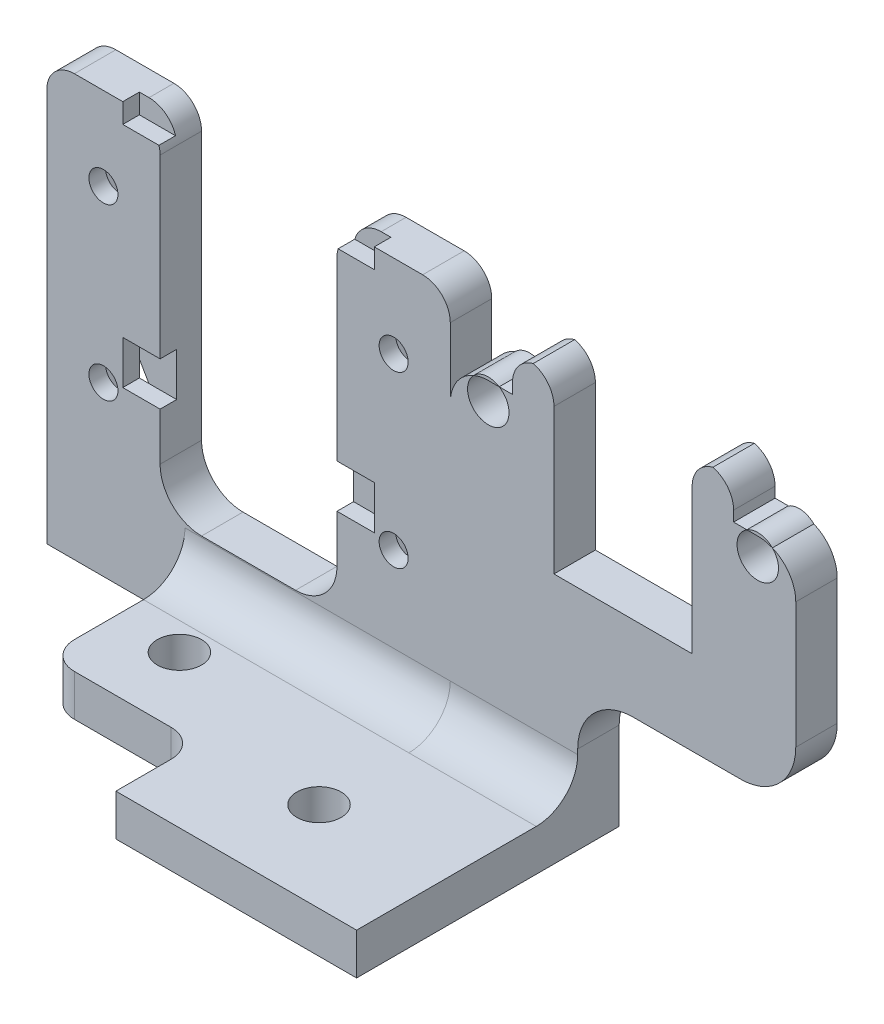
SolidWorks part; units mm, degrees
ref_plane "Plano frontal" through (0, 0, 0) normal (0, 0, 1) x (1, 0, 0)
ref_plane "Plano superior" through (0, 0, 0) normal (0, 1, 0) x (1, 0, 0)
ref_plane "Plano direito" through (0, 0, 0) normal (1, 0, 0) x (0, 0, -1)
sketch "Esboço2" plane through (0, 0, -1) normal (0, 0, -1) x (-1, 0, 0)
  line L1 (14.6, 8.1) -> (6.4, 8.1)
  line L2 (14.6, 8.1) -> (14.6, -22.3604)
  line L3 (14.6, -22.3604) -> (6.4, -22.3604)
  line L4 (6.4, 8.1) -> (6.4, -22.3604)
  line L5 (6.4, 8.1) -> (-21.6025, 8.1) construction
  line L6 (-12.6, -12) -> (-12.6, 12) construction
  line L7 (-14.6, 8.1) -> (-6.4, 8.1)
  line L8 (-14.6, 8.1) -> (-14.6, -22.3604)
  line L9 (-14.6, -22.3604) -> (-6.4, -22.3604)
  line L10 (-6.4, 8.1) -> (-6.4, -22.3604)
  line L11 (12.6, -12) -> (12.6, 12) construction
  line L12 (-4.4, -2.7) -> (-4.4, 6.1) construction
  circle A0 centre (-10.5, 2.1) radius 1.05 construction
  dimension "D3" = 6
  dimension "D1" = 2
  dimension "D2" = 2
  dimension "D4" = 2
extrude "Ressalto-extrusão1" add sketch "Esboço2" along normal blind 3
sketch "Esboço3" plane through (-6.4, 0, 0) normal (1, 0, 0) x (0, 0, -1)
  line L0 (4, 8.1) -> (4, -22.3604) construction
  line L1 (1, -22.3604) -> (4, -22.3604)
  line L2 (1, -22.3604) -> (1, -16.2722)
  line L3 (1, -16.2722) -> (4, -16.2722)
  line L4 (4, -22.3604) -> (4, -16.2722)
extrude "Ressalto-extrusão2" add sketch "Esboço3" along normal up to next
sketch "Esboço4" plane through (0, 0, -1) normal (0, 0, 1) x (1, 0, 0)
  line L0 (14.6, -22.3604) -> (-14.6, -22.3604) construction
  line L1 (-6.4, -22.3604) -> (6.4, -22.3604)
  line L2 (-6.4, -22.3604) -> (-6.4, -19.3604)
  line L3 (-6.4, -19.3604) -> (6.4, -19.3604)
  line L4 (6.4, -22.3604) -> (6.4, -19.3604)
  line L5 (6.4, -16.2722) -> (6.4, 8.1) construction
  line L6 (-6.4, 8.1) -> (-6.4, -16.2722) construction
  dimension "D1" = 3
extrude "Ressalto-extrusão3" add sketch "Esboço4" along normal blind 10
sketch "Esboço5" plane through (0, 0, -1) normal (0, 0, 1) x (1, 0, 0)
  line L0 (14.6, 8.1) -> (14.6, -22.3604) construction
  line L1 (-14.6, -22.3604) -> (-6.4, -22.3604)
  line L2 (-14.6, -22.3604) -> (-14.6, -19.3604)
  line L3 (-14.6, -19.3604) -> (-6.4, -19.3604)
  line L4 (-6.4, -22.3604) -> (-6.4, -19.3604)
  line L5 (6.4, -22.3604) -> (14.6, -22.3604)
  line L6 (6.4, -22.3604) -> (6.4, -19.3604)
  line L7 (6.4, -19.3604) -> (14.6, -19.3604)
  line L8 (14.6, -22.3604) -> (14.6, -19.3604)
  line L9 (-6.4, -19.3604) -> (-6.4, -22.3604) construction
  dimension "D1" = 3
extrude "Ressalto-extrusão4" add sketch "Esboço5" along normal blind 16
sketch "Esboço6" plane through (0, -19.3604, 0) normal (0, 1, 0) x (1, 0, 0)
  line L0 (6.4, -9) -> (-6.4, 1) construction
  line L1 (6.4, -15) -> (6.4, -9) construction
  line L2 (-14.6, -10.5) -> (-6.4, -10.5) construction
  line L3 (-14.6, -15) -> (-14.6, 1) construction
  line L4 (-6.4, -15) -> (-6.4, -9) construction
  line L5 (-6.4, -10.5) -> (6.4, -10.5) construction
  line L6 (6.4, -10.5) -> (14.6, -10.5) construction
  line L7 (14.6, -15) -> (14.6, 1) construction
  line L8 (14.6, -15) -> (6.4, -15) construction
  circle A0 centre (0, -4) radius 1.6
  circle A1 centre (10.5, -10.5) radius 1.6
  circle A2 centre (-10.5, -10.5) radius 1.6
  dimension "D1" = 3.2
  dimension "D2" = 4.5
sketch "Esboço8" plane through (0, 0, -1) normal (0, 0, 1) x (1, 0, 0)
  circle A0 centre (-10.5, 2.1) radius 1.05
  circle A1 centre (10.5, 2.1) radius 1.05
  circle A2 centre (10.5, -10.2) radius 1.05
  circle A3 centre (-10.5, -10.2) radius 1.05
  dimension "D1" = 2.1
extrude "Corte-extrusão3" cut sketch "Esboço8" against normal through all
fillet "Filete1" radius 3 2 edges at (6.4, -16.2722, -2.5) (-6.4, -16.2722, -2.5)
sketch "Esboço9" plane through (6.4, 0, 0) normal (-1, 0, 0) x (0, 0, 1)
  line L0 (-1, -13.2722) -> (-1, 8.1) construction
  line L1 (-1, -6.6712) -> (-2.2, -6.6712)
  line L2 (-1, -6.6712) -> (-1, -9.82)
  line L3 (-1, -9.82) -> (-2.2, -9.82)
  line L4 (-2.2, -6.6712) -> (-2.2, -9.82)
extrude "Corte-extrusão4" cut sketch "Esboço9" against normal blind 2.7
fillet "Filete2" radius 3 1 edges at (0, -19.3604, -1)
sketch "Esboço10" plane through (0, 0, -4) normal (0, 0, -1) x (-1, 0, 0)
  line L0 (0, -16.2722) -> (0, 4.5459) construction
  line L1 (12.8094, 2.1) -> (11.6547, 4.1)
  line L2 (11.6547, 4.1) -> (9.3453, 4.1)
  line L3 (9.3453, 4.1) -> (8.1906, 2.1)
  line L4 (8.1906, 2.1) -> (9.3453, 0.1)
  line L5 (9.3453, 0.1) -> (11.6547, 0.1)
  line L6 (11.6547, 0.1) -> (12.8094, 2.1)
  line L7 (12.8094, -10.2) -> (11.6547, -8.2)
  line L8 (11.6547, -8.2) -> (9.3453, -8.2)
  line L9 (9.3453, -8.2) -> (8.1906, -10.2)
  line L10 (8.1906, -10.2) -> (9.3453, -12.2)
  line L11 (9.3453, -12.2) -> (11.6547, -12.2)
  line L12 (11.6547, -12.2) -> (12.8094, -10.2)
  line L13 (-3.4, -16.2722) -> (3.4, -16.2722) construction
  line L14 (-11.6547, -12.2) -> (-12.8094, -10.2)
  line L15 (-9.3453, -12.2) -> (-11.6547, -12.2)
  line L16 (-8.1906, -10.2) -> (-9.3453, -12.2)
  line L17 (-9.3453, -8.2) -> (-8.1906, -10.2)
  line L18 (-11.6547, -8.2) -> (-9.3453, -8.2)
  line L19 (-12.8094, -10.2) -> (-11.6547, -8.2)
  line L20 (-11.6547, 0.1) -> (-12.8094, 2.1)
  line L21 (-9.3453, 0.1) -> (-11.6547, 0.1)
  line L22 (-8.1906, 2.1) -> (-9.3453, 0.1)
  line L23 (-9.3453, 4.1) -> (-8.1906, 2.1)
  line L24 (-11.6547, 4.1) -> (-9.3453, 4.1)
  line L25 (-12.8094, 2.1) -> (-11.6547, 4.1)
  circle A0 centre (10.5, 2.1) radius 2 construction
  circle A1 centre (10.5, -10.2) radius 2 construction
  circle A2 centre (-10.5, -10.2) radius 2 construction
  circle A3 centre (-10.5, 2.1) radius 2 construction
  point P25 (10.5, 0.1)
  dimension "D1" = 4
extrude "Corte-extrusão5" cut sketch "Esboço10" against normal blind 1.8
sketch "Esboço11" plane through (0, -19.3604, 0) normal (0, 1, 0) x (1, 0, 0)
  line L0 (0, 0) -> (0, -34) construction
  line L1 (8.25, -11) -> (-8.25, -11)
  line L2 (8.25, -11) -> (8.25, -17)
  line L3 (8.25, -17) -> (-8.25, -17)
  line L4 (-8.25, -11) -> (-8.25, -17)
  line L5 (6.4, -9) -> (-6.4, -9) construction
  point P7 (0, -17)
  dimension "D1" = 16.5
  dimension "D2" = 6
  dimension "D3" = 2
sketch "Esboço13" plane through (0, 0, -1) normal (0, 0, 1) x (1, 0, 0)
  line L0 (12.6426, 0) -> (0, 0) construction
  line L1 (12.6426, 12) -> (12.6426, -12) construction
  line L2 (9.1, -6.6712) -> (6.4, -6.6712) construction
  line L3 (6.4, -6.6712) -> (6.4, -9.82) construction
  line L4 (9.1, -9.82) -> (6.4, -9.82) construction
  line L5 (9.1, -9.82) -> (9.1, -6.6712) construction
  line L6 (9.1, -6.6712) -> (6.4, -6.6712)
  line L7 (6.4, -6.6712) -> (6.4, -9.82)
  line L8 (9.1, -9.82) -> (6.4, -9.82)
  line L9 (9.1, -9.82) -> (9.1, -6.6712)
  line L10 (0, 0) -> (0, -9.82) construction
  line L11 (9.1, 9.82) -> (9.1, 6.6712)
  line L12 (9.1, 9.82) -> (6.4, 9.82)
  line L13 (6.4, 6.6712) -> (6.4, 9.82)
  line L14 (9.1, 6.6712) -> (6.4, 6.6712)
  line L15 (-9.1, 6.6712) -> (-6.4, 6.6712)
  line L16 (-6.4, 6.6712) -> (-6.4, 9.82)
  line L17 (-9.1, 9.82) -> (-6.4, 9.82)
  line L18 (-9.1, 9.82) -> (-9.1, 6.6712)
  line L19 (-9.1, -9.82) -> (-9.1, -6.6712)
  line L20 (-9.1, -9.82) -> (-6.4, -9.82)
  line L21 (-6.4, -6.6712) -> (-6.4, -9.82)
  line L22 (-9.1, -6.6712) -> (-6.4, -6.6712)
extrude "Corte-extrusão7" cut sketch "Esboço13" against normal up to surface (1.2 mm away) up to face at (7.882, -8.3215, -2.2)
sketch "Esboço14" plane through (14.6, 0, 0) normal (1, 0, 0) x (0, 0, -1)
  line L0 (-15, -19.3604) -> (4, -19.3604)
  line L1 (4, 8.1) -> (4, -22.3604) construction
  line L2 (4, -19.3604) -> (4, -22.3604)
  line L3 (4, -22.3604) -> (-15, -22.3604)
  line L4 (-15, -22.3604) -> (-15, -19.3604)
extrude "Ressalto-extrusão5" add sketch "Esboço14" along normal blind 25
sketch "Esboço15" plane through (0, -19.3604, 0) normal (0, 1, 0) x (1, 0, 0)
  line L0 (14.6, 1) -> (39.6, 1)
  line L1 (39.6, 4) -> (39.6, -15) construction
  line L2 (39.6, 1) -> (39.6, 4)
  line L3 (39.6, 4) -> (14.6, 4)
  line L4 (14.6, 4) -> (14.6, 1)
  dimension "D1" = 3
extrude "Ressalto-extrusão6" add sketch "Esboço15" along normal blind 25.96
sketch "Esboço16" plane through (0, 0, -4) normal (0, 0, -1) x (-1, 0, 0)
  line L0 (-14.6, 8.1) -> (-14.6, -16.6485) construction
  line L1 (-39.6, 1.0996) -> (-14.6, 1.0996) construction
  line L2 (-39.6, -22.3604) -> (-39.6, 6.5996) construction
  line L3 (-39.6, 6.5996) -> (-14.6, 6.5996) construction
  line L4 (-27.1, 6.5996) -> (-27.1, -12.0071) construction
  line L5 (-35.1, 6.5996) -> (-35.1, 3.8496) construction
  line L6 (-35.1, 3.8496) -> (-36.85, 3.8496)
  line L7 (-36.85, -1.6504) -> (-35.1, -1.6504)
  line L8 (-35.1, -1.6504) -> (-35.1, -7.4004)
  line L9 (-36.85, 3.8496) -> (-36.85, -4.4528) construction
  line L10 (-35.1, 6.5996) -> (-35.1, 3.8496)
  line L11 (-35.1, 6.5996) -> (-32.1, 6.5996)
  line L12 (-32.1, 6.5996) -> (-32.1, -5.9004)
  line L13 (-35.1, -7.4004) -> (-35.1, -10.4004)
  line L14 (-35.1, -10.4004) -> (-27.1, -10.4004)
  line L15 (-32.1, -5.9004) -> (-22.1, -5.9004)
  line L16 (-19.1, -7.4004) -> (-19.1, -10.4004)
  line L17 (-19.1, -1.6504) -> (-19.1, -7.4004)
  line L18 (-17.35, -1.6504) -> (-19.1, -1.6504)
  line L19 (-19.1, 3.8496) -> (-17.35, 3.8496)
  line L20 (-19.1, 6.5996) -> (-19.1, 3.8496)
  line L21 (-19.1, 6.5996) -> (-22.1, 6.5996)
  line L22 (-22.1, 6.5996) -> (-22.1, -5.9004)
  line L23 (-27.1, -10.4004) -> (-19.1, -10.4004)
  line L24 (-32.1, 6.5996) -> (-22.1, 6.5996)
  line L25 (-39.6, -12.0071) -> (-27.1, -12.0071)
  line L27 (-23.82, -19.3604) -> (-39.6, -19.3604)
  line L28 (-39.6, -22.3604) -> (14.6, -22.3604) construction
  line L29 (-14.6, 8.1) -> (-14.6, 1.0996)
  line L30 (-19.1, 6.5996) -> (-14.6, 8.1)
  line L31 (-39.6, -12.0071) -> (-39.6, -19.3604)
  line L32 (-23.82, -19.3604) -> (-23.82, -12.0071)
  line L33 (-23.82, -12.0071) -> (-27.1, -12.0071)
  arc A0 (-36.85, 3.8496) -> (-36.85, -1.6504) centre (-36.85, 1.0996) ccw
  circle A1 centre (-36.85, 2.5741) radius 1.5
  circle A2 centre (-17.35, 2.5741) radius 1.5
  arc A3 (-17.35, 3.8496) -> (-17.35, -1.6504) centre (-17.35, 1.0996) cw
  point P38 (-27.1, -5.9004)
  dimension "D6" = 1.75
  dimension "D1" = 5.5
  dimension "D2" = 12.5
  dimension "D3" = 2.75
  dimension "D4" = 1.75
  dimension "D5" = 8
  dimension "D7" = 5.75
  dimension "D8" = 3
  dimension "D9" = 3
  dimension "D10" = 3
  dimension "D11" = 15.78
extrude "Corte-extrusão8" cut sketch "Esboço16" against normal blind 26
fillet "Filete4" radius 4 1 edges at (39.6, -12.0071, -2.5)
fillet "Filete5" radius 2 16 edges at (6.4, 7.3856, -2.2) (6.4, 6.6712, -1.6) (-6.4, 7.3856, -2.2) (32.1, 6.5996, -2.5) (19.1, 6.5996, -2.5) (33.6, 6.5996, -1) (35.1, 6.5996, -2.5) (33.6, 6.5996, -4) (20.6, 6.5996, -1) (22.1, 6.5996, -2.5) (20.6, 6.5996, -4) (14.6, 8.1, -2.5) (-6.4, 8.1, -3.1) (-6.4, 6.6712, -1.6) (-14.6, 8.1, -2.5) (6.4, 8.1, -3.1)
sketch "Esboço18" plane through (-14.6, 0, 0) normal (-1, 0, 0) x (0, 0, 1)
  line L0 (-1, -16.3604) -> (-1, -22.3604)
  line L1 (-4, -22.3604) -> (15, -22.3604) construction
  line L2 (-1, -22.3604) -> (15, -22.3604)
  line L3 (15, -22.3604) -> (15, -19.3604)
  line L4 (15, -19.3604) -> (-1, -16.3604)
extrude "Corte-extrusão10" cut sketch "Esboço18" against normal blind 10
sketch "Esboço19" plane through (39.6, 0, 0) normal (1, 0, 0) x (0, 0, -1)
  line L0 (-15, -17.3604) -> (-15, -22.3604)
  line L1 (-15, -22.3604) -> (4, -22.3604)
  line L2 (4, -22.3604) -> (4, -17.3604)
  line L3 (4, -17.3604) -> (-15, -17.3604)
  dimension "D1" = 5
extrude "Corte-extrusão13" cut sketch "Esboço19" against normal blind 15.78
fillet "Filete7" radius 4 1 edges at (23.82, -12.0071, -2.5)
fillet "Filete8" radius 3 3 edges at (14.6, -17.8604, -1) (19.21, -19.3604, -1) (14.6, -19.3604, 0.5)
sketch "Esboço20" plane through (0, -19.3604, 0) normal (0, 1, 0) x (1, 0, 0)
  line L0 (14.6, -2) -> (14.6, -15) construction
  line L1 (23.82, -15) -> (6.4, -15) construction
  circle A0 centre (14.6, -8.5) radius 1.6
  circle A1 centre (0, -4) radius 1.6
extrude "Corte-extrusão14" cut sketch "Esboço20" against normal blind 12
fillet "Filete9" radius 2 2 edges at (6.4, -20.8604, 9) (-4.6, -20.8604, 9)
